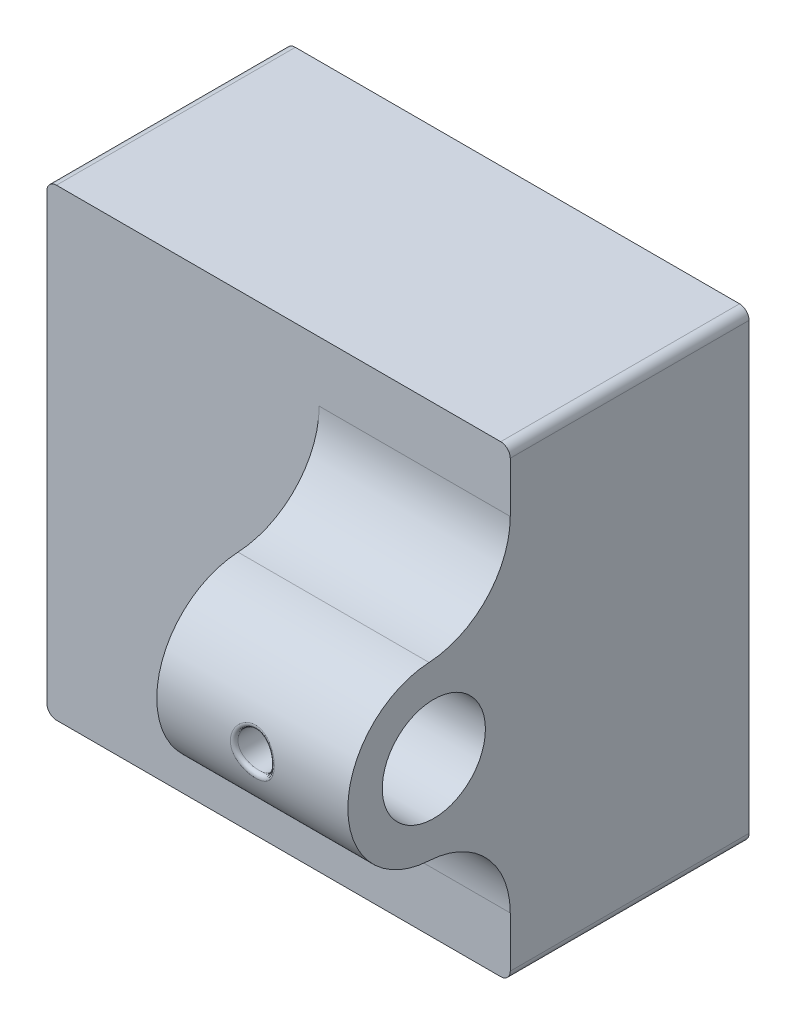
SolidWorks part; units mm, degrees
ref_plane "Front Plane" through (0, 0, 0) normal (0, 0, 1) x (1, 0, 0)
ref_plane "Top Plane" through (0, 0, 0) normal (0, 1, 0) x (1, 0, 0)
ref_plane "Right Plane" through (0, 0, 0) normal (1, 0, 0) x (0, 0, -1)
ref_plane "Plane1" through (14.25, 0, 0) normal (1, 0, 0) x (0, 0, -1)
sketch "Sketch2" plane through (0, 0, 0) normal (0, 0, 1) x (1, 0, 0)
  line L0 (-23.25, 24.25) -> (23.25, 24.25)
  line L1 (-19.25, 20.25) -> (19.25, 20.25)
  line L2 (-20.25, 19.25) -> (-20.25, -19.25)
  line L3 (-19.25, -20.25) -> (19.25, -20.25)
  line L4 (20.25, 19.25) -> (20.25, -19.25)
  line L5 (-20.25, 20.25) -> (20.25, -20.25) construction
  line L6 (-20.25, -20.25) -> (20.25, 20.25) construction
  line L7 (24.25, 23.25) -> (24.25, -23.25)
  line L8 (-23.25, -24.25) -> (23.25, -24.25)
  line L9 (-24.25, 23.25) -> (-24.25, -23.25)
  line L10 (-20.25, 20.25) -> (-20.25, -20.25) construction
  line L11 (-20.25, -20.25) -> (20.25, -20.25) construction
  line L12 (20.25, 20.25) -> (20.25, -20.25) construction
  line L13 (-20.25, 20.25) -> (20.25, 20.25) construction
  line L14 (-24.25, 24.25) -> (24.25, 24.25) construction
  line L15 (24.25, 24.25) -> (24.25, -24.25) construction
  line L16 (-24.25, -24.25) -> (24.25, -24.25) construction
  line L17 (-24.25, 24.25) -> (-24.25, -24.25) construction
  line L19 (14.25, 4) -> (26.25, 4)
  line L20 (14.25, 4) -> (14.25, -4)
  line L21 (14.25, -4) -> (26.25, -4)
  line L22 (26.25, 4) -> (26.25, -4)
  line L23 (14.25, 4) -> (26.25, -4) construction
  line L24 (14.25, -4) -> (26.25, 4) construction
  arc A0 (-20.25, -19.25) -> (-19.25, -20.25) centre (-19.25, -19.25) ccw
  arc A1 (19.25, -20.25) -> (20.25, -19.25) centre (19.25, -19.25) ccw
  arc A2 (19.25, 20.25) -> (20.25, 19.25) centre (19.25, 19.25) cw
  arc A3 (-19.25, 20.25) -> (-20.25, 19.25) centre (-19.25, 19.25) ccw
  arc A4 (23.25, 24.25) -> (24.25, 23.25) centre (23.25, 23.25) cw
  arc A5 (24.25, -23.25) -> (23.25, -24.25) centre (23.25, -23.25) cw
  arc A6 (-23.25, -24.25) -> (-24.25, -23.25) centre (-23.25, -23.25) cw
  arc A7 (-23.25, 24.25) -> (-24.25, 23.25) centre (-23.25, 23.25) ccw
  point P0 (0, 0)
  point P35 (20.25, 0)
  dimension "D3" = 1
  dimension "D4" = 1
  dimension "D1" = 40.5
  dimension "D5" = 8
  dimension "D6" = 6
  dimension "D2" = 4
extrude "Boss-Extrude1" add sketch "Sketch2" along normal blind 5 contours L1 A3 L2 A0 L3 A1 L4 L21 L20 L19 A2 | L0 A7 L9 A6 L8 A5 L7 L21 L4 A1 L3 A0 L2 A3 L1 A2 L19 A4 | L4 L21 L7 L19 | L20 L21 L4 L19 region at (0, 23.5641, 0) region at (22.25, 0, 0) region at (-0.5203, 0, 0) region at (17.25, 0, 0)
sketch "Sketch3" plane through (14.25, 0, 0) normal (1, 0, 0) x (0, 0, -1)
  line L0 (-5, 23.25) -> (-5, -23.25) construction
  line L1 (-5, 23.25) -> (-5, 17.9722)
  line L2 (-5, -17.9722) -> (-5, -23.25)
  line L3 (-5, 23.25) -> (-5, -23.25)
  circle A0 centre (-13, 0) radius 5.4
  arc A2 (-13.5, 8.9861) -> (-13.5, -8.9861) centre (-13, 0) ccw
  arc A3 (-13.5, -8.9861) -> (-5, -17.9722) centre (-14, -17.9722) cw
  arc A4 (-13.5, 8.9861) -> (-5, 17.9722) centre (-14, 17.9722) ccw
  point P9 (-5, -4.1231)
  dimension "D1" = 10.8
  dimension "D3" = 9
  dimension "D4" = 9
  dimension "D2" = 8
extrude "Boss-Extrude2" add sketch "Sketch3" along normal mid plane 20 contours A4 A2 A3 L3 A0 region at (14.25, 0, 5.3976)
extrude "Boss-Extrude3" add sketch "Sketch2<3>" against normal blind 20 contours L20 L21 L4 L19 | L0 A7 L9 A6 L8 A5 L7 L21 L4 A1 L3 A0 L2 A3 L1 A2 L19 A4 | L4 L21 L7 L19 region at (0, 23.5641, 0) region at (22.25, 0, 0) region at (17.25, 0, 0)
sketch "Sketch2<3>" plane through (0, 0, 0) normal (0, 0, 1) x (1, 0, 0) same geometry as "Sketch2"
fillet "Fillet1" radius 2 2 edges at (14.25, -4, -10) (14.25, 4, -10)
ref_plane "Plane2" through (0, 0, 22) normal (0, 0, 1) x (1, 0, 0)
sketch "Sketch4" plane through (0, 0, 22) normal (0, 0, 1) x (1, 0, 0)
  line L0 (14.25, -23.65) -> (14.25, 23.65) construction
  circle A0 centre (14.25, 0) radius 1.9
  dimension "D1" = 3.8
extrude "Cut-Extrude1" cut sketch "Sketch4" against normal blind 10
fillet "Fillet2" radius 0.4 1 edges at (12.3905, 0.39, 21.9915)
